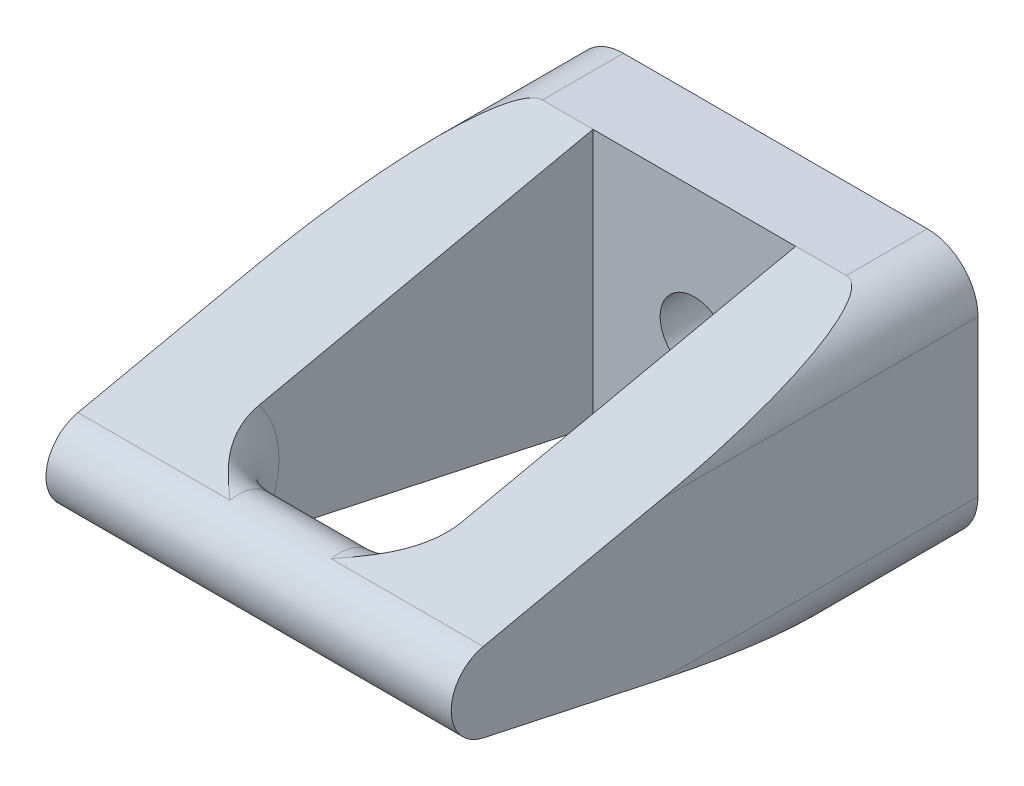
SolidWorks part; units mm, degrees
ref_plane "Front Plane" through (0, 0, 0) normal (0, 0, 1) x (1, 0, 0)
ref_plane "Top Plane" through (0, 0, 0) normal (0, 1, 0) x (1, 0, 0)
ref_plane "Right Plane" through (0, 0, 0) normal (1, 0, 0) x (0, 0, -1)
sketch "Sketch1" plane through (0, 0, 0) normal (0, 0, 1) x (1, 0, 0)
  line L0 (-7, 0) -> (7, 0) construction
  line L2 (-20, -12.7) -> (20, -12.7)
  line L3 (-20, -12.7) -> (-20, 12.7)
  line L4 (-20, 12.7) -> (20, 12.7)
  line L5 (20, -12.7) -> (20, 12.7)
  line L6 (-20, -12.7) -> (20, 12.7) construction
  line L7 (-20, 12.7) -> (20, -12.7) construction
  point P0 (0, 0)
  point P4 (0, 0)
  dimension "D1" = 14
  dimension "D2" = 25.4
  dimension "D3" = 40
extrude "Boss-Extrude1" add sketch "Sketch1" along normal blind 8
sketch "Sketch4" plane through (-20, 0, 0) normal (-1, 0, 0) x (0, 0, 1)
  line L0 (8, 12.7) -> (48.8416, 3.9105)
  line L1 (48.8416, -3.9105) -> (8, -12.7)
  line L2 (8, -12.7) -> (8, 12.7)
  arc A0 (48.8416, 3.9105) -> (48.8416, -3.9105) centre (48, 0) cw
  dimension "D1" = 40
  dimension "D2" = 4
extrude "Boss-Extrude2" add sketch "Sketch4" against normal blind 10
mirror "Mirror1" about plane through (0, 0, 0) normal (1, 0, 0) of "Boss-Extrude2"
sketch "Sketch5" plane through (10, 0, 0) normal (-1, 0, 0) x (0, 0, 1)
  circle A0 centre (48, 0) radius 4
  arc A1 (48.8416, -3.9105) -> (48.8416, 3.9105) centre (48, 0) ccw construction
extrude "Boss-Extrude3" add sketch "Sketch5" along normal up to surface (20 mm away) up to face at (-10, 0, 29.2104)
fillet "Fillet1" radius 5 4 edges at (20, 12.7, 4) (-20, -12.7, 4) (20, -12.7, 4) (-20, 12.7, 4)
fillet "Fillet2" radius 5 2 edges at (10, 0, 44) (-10, 0, 44)
hole_wizard "1/4 Clearance Hole1" positions "Sketch6" profile "Sketch7" hole size "1/4" standard "ANSI Inch" end condition up to next
sketch "Sketch6" plane through (0, 0, 0) normal (0, 0, -1) x (-1, 0, 0)
  point P0 (0, 0)
sketch "Sketch7" plane through (0, 0, 0) normal (1, 0, 0) x (0, 1, 0)
  line L0 (0, 0) -> (0, 8)
  line L1 (0, 8) -> (3.3782, 8)
  line L2 (3.3782, 8) -> (3.3782, 0)
  line L5 (3.3782, 0) -> (0, 0)
  line L11 (0, -6.35) -> (0, 107.95) construction
  dimension "Thru Hole Dia." = 6.7564
  dimension "Thru Hole Depth" = 8
